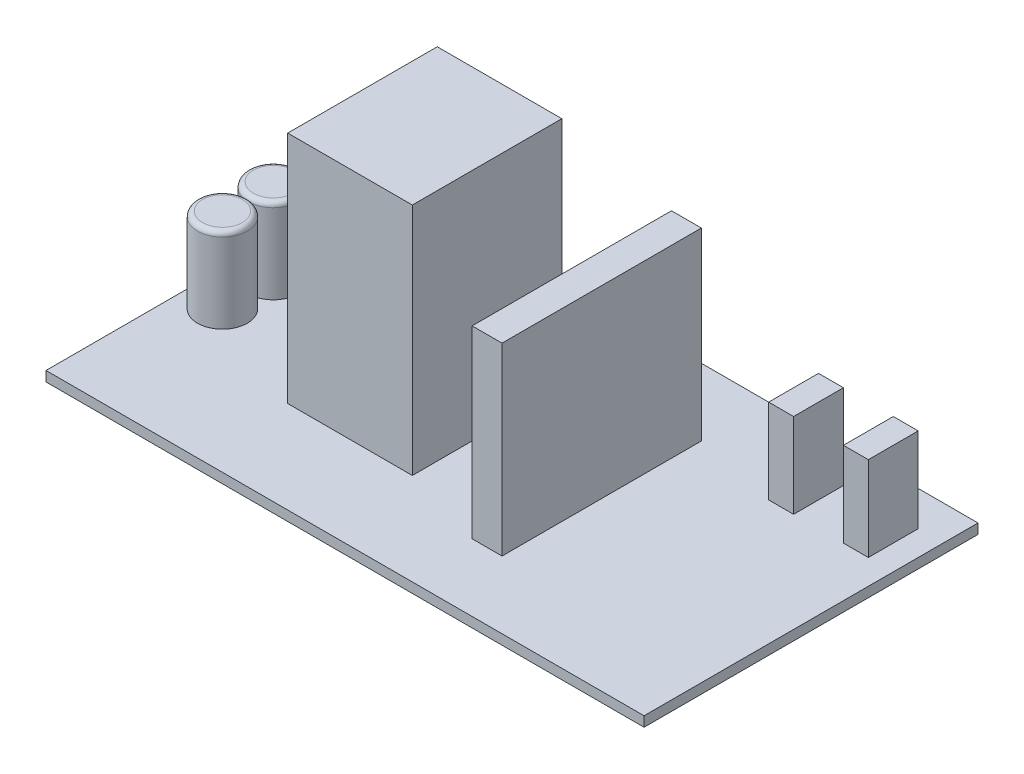
SolidWorks part; units mm, degrees
ref_plane "Front Plane" through (0, 0, 0) normal (0, 0, 1) x (1, 0, 0)
ref_plane "Top Plane" through (0, 0, 0) normal (0, 1, 0) x (1, 0, 0)
ref_plane "Right Plane" through (0, 0, 0) normal (1, 0, 0) x (0, 0, -1)
sketch "Sketch1" plane through (0, 0, 0) normal (0, 1, 0) x (1, 0, 0)
  line L1 (-60, 33.5) -> (60, 33.5)
  line L2 (-60, 33.5) -> (-60, -33.5)
  line L3 (-60, -33.5) -> (60, -33.5)
  line L4 (60, 33.5) -> (60, -33.5)
  line L5 (-60, 33.5) -> (60, -33.5) construction
  line L6 (-60, -33.5) -> (60, 33.5) construction
  point P0 (0, 0)
  dimension "D1" = 67
  dimension "D2" = 120
extrude "Boss-Extrude1" add sketch "Sketch1" along normal blind 2
sketch "Sketch2" plane through (0, 2, 0) normal (0, 1, 0) x (1, 0, 0)
  line L0 (-60, 33.5) -> (-60, -33.5) construction
  circle A0 centre (-53, 5.1) radius 5
  circle A1 centre (-53, -5.1) radius 5
  dimension "D1" = 10
  dimension "D4" = 10.2
  dimension "D2" = 5.1
  dimension "D3" = 7
extrude "Boss-Extrude2" add sketch "Sketch2" along normal blind 17
fillet "Fillet1" radius 1 2 edges at (-53, 19, 10.1) (-53, 19, -0.1)
sketch "Sketch3" plane through (0, 2, 0) normal (0, 1, 0) x (1, 0, 0)
  line L0 (60, -33.5) -> (60, 33.5) construction
  line L1 (-30, 15) -> (-5, 15)
  line L2 (-30, 15) -> (-30, -15)
  line L3 (-30, -15) -> (-5, -15)
  line L4 (-5, 15) -> (-5, -15)
  line L5 (12, 20) -> (18, 20)
  line L6 (12, 20) -> (12, -20)
  line L7 (12, -20) -> (18, -20)
  line L8 (18, 20) -> (18, -20)
  line L9 (55, 26.5) -> (50, 26.5)
  line L10 (55, 26.5) -> (55, 16.5)
  line L11 (55, 16.5) -> (50, 16.5)
  line L12 (50, 26.5) -> (50, 16.5)
  line L13 (60, 33.5) -> (-60, 33.5) construction
  line L14 (40, 26.5) -> (35, 26.5)
  line L15 (40, 26.5) -> (40, 16.5)
  line L16 (40, 16.5) -> (35, 16.5)
  line L17 (35, 26.5) -> (35, 16.5)
  dimension "D1" = 5
  dimension "D2" = 10
  dimension "D3" = 5
  dimension "D4" = 7
  dimension "D5" = 5
  dimension "D6" = 10
  dimension "D7" = 10
  dimension "D8" = 40
  dimension "D9" = 20
  dimension "D10" = 6
  dimension "D11" = 12
  dimension "D12" = 25
  dimension "D13" = 30
  dimension "D14" = 15
  dimension "D15" = 5
extrude "Boss-Extrude3" add sketch "Sketch3" along normal blind 47 contours L4 L1 L2 L3 region at (-17.5, 2, 0)
extrude "Boss-Extrude4" add sketch "Sketch3<3>" along normal blind 37 contours L8 L5 L6 L7 region at (15, 2, 0)
sketch "Sketch3<3>" plane through (0, 2, 0) normal (0, 1, 0) x (1, 0, 0) same geometry as "Sketch3"
extrude "Boss-Extrude5" add sketch "Sketch3<4>" along normal blind 17 contours L14 L17 L16 L15 | L9 L12 L11 L10 region at (52.5, 2, -21.5) region at (37.5, 2, -21.5)
sketch "Sketch3<4>" plane through (0, 2, 0) normal (0, 1, 0) x (1, 0, 0) same geometry as "Sketch3"
